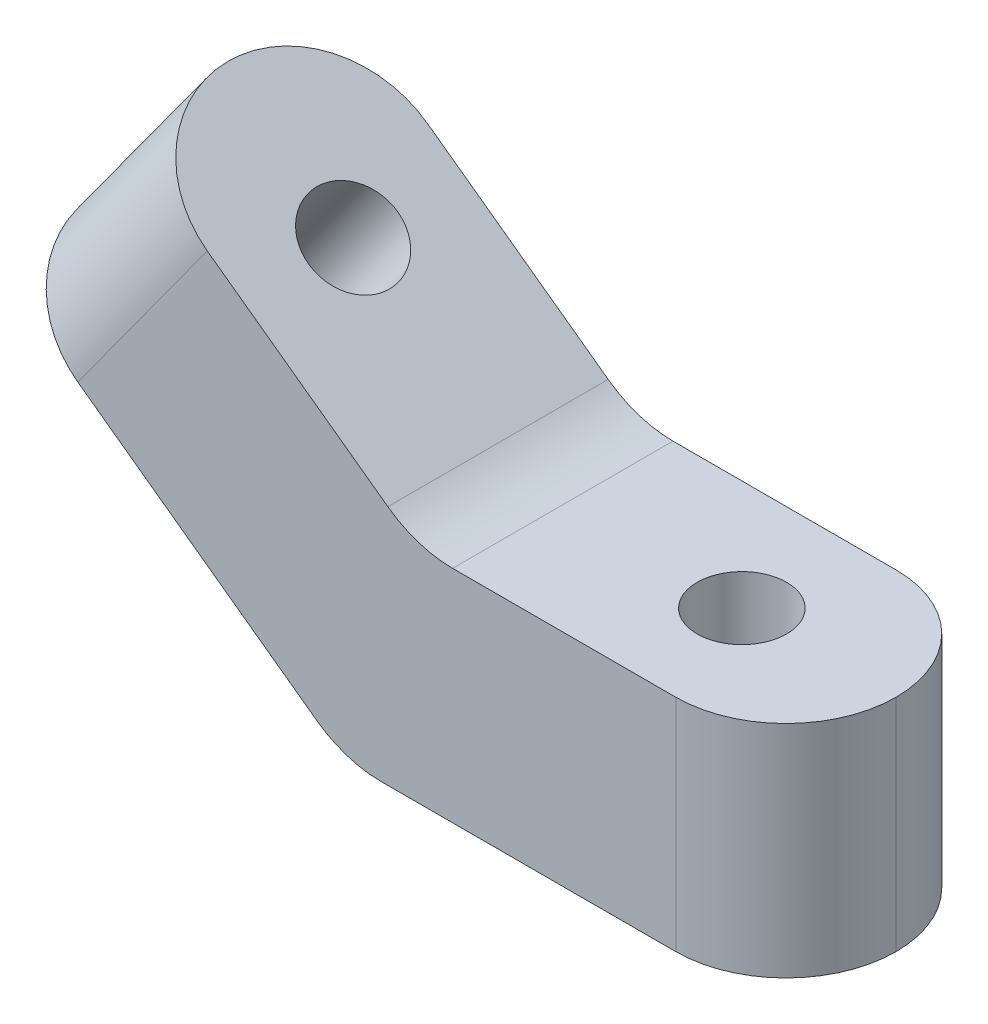
SolidWorks part; units mm, degrees
ref_plane "Front Plane" through (0, 0, 0) normal (0, 0, 1) x (1, 0, 0)
ref_plane "Top Plane" through (0, 0, 0) normal (0, 1, 0) x (1, 0, 0)
ref_plane "Right Plane" through (0, 0, 0) normal (1, 0, 0) x (0, 0, -1)
sketch "Sketch1" plane through (0, 0, 0) normal (0, 0, 1) x (1, 0, 0)
  line L0 (27.8088, 8.0057) -> (6.5352, 8.0057)
  line L1 (6.5352, 8.0057) -> (-10.6754, 20.5099)
  line L2 (-10.6754, 20.5099) -> (-18.1403, 10.2354)
  line L3 (-18.1403, 10.2354) -> (2.4088, -4.6943)
  line L4 (2.4088, -4.6943) -> (27.8088, -4.6943)
  line L5 (27.8088, -4.6943) -> (27.8088, 8.0057)
  dimension "D1" = 144
  dimension "D2" = 12.7
  dimension "D3" = 90
  dimension "D4" = 12.7
  dimension "D5" = 25.4
  dimension "D6" = 25.4
extrude "Boss-Extrude1" add sketch "Sketch1" along normal blind 12.7
sketch "Sketch2" plane through (0, 8.0057, 0) normal (0, 1, 0) x (1, 0, 0)
  line L0 (27.8088, -12.7) -> (6.5352, -12.7) construction
  line L1 (27.8088, -12.7) -> (27.8088, 0) construction
  circle A0 centre (18.9188, -6.35) radius 2.5797
  dimension "D3" = 5.1594
  dimension "D1" = 6.35
  dimension "D2" = 8.89
extrude "Cut-Extrude1" cut sketch "Sketch2" against normal blind 26.162
sketch "Sketch3" plane through (6.0648, 8.3475, 0) normal (0.5878, 0.809, 0) x (0.809, -0.5878, 0)
  line L0 (-20.692, -12.7) -> (-20.692, 0) construction
  line L1 (0.5815, 0) -> (-20.692, 0) construction
  circle A0 centre (-11.802, -6.35) radius 2.5797
  dimension "D3" = 5.1594
  dimension "D1" = 8.89
  dimension "D2" = 6.35
extrude "Cut-Extrude2" cut sketch "Sketch3" against normal blind 26.162
fillet "Fillet1" radius 6.35 4 edges at (-14.4078, 15.3727, 0) (-14.4078, 15.3727, 12.7) (27.8088, 1.6557, 0) (27.8088, 1.6557, 12.7)
fillet "Fillet2" radius 6.35 2 edges at (6.5352, 8.0057, 6.35) (2.4088, -4.6943, 6.35)
